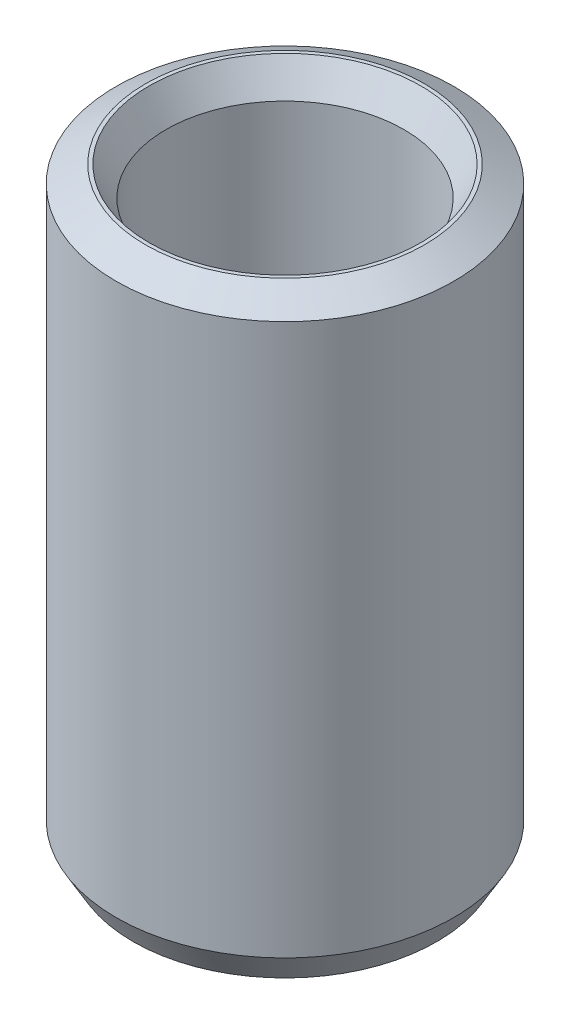
SolidWorks part; units mm, degrees
ref_plane "Front Plane" through (0, 0, 0) normal (0, 0, 1) x (1, 0, 0)
ref_plane "Top Plane" through (0, 0, 0) normal (0, 1, 0) x (1, 0, 0)
ref_plane "Right Plane" through (0, 0, 0) normal (1, 0, 0) x (0, 0, -1)
sketch "Sketch1" plane through (0, 0, 0) normal (0, 1, 0) x (1, 0, 0)
  circle A0 centre (0, 0) radius 15
  dimension "SLEEVE_OD" = 30
extrude "Boss-Extrude1" add sketch "Sketch1" along normal blind 53.0629
sketch "Sketch2" plane through (0, 0, 0) normal (0, 1, 0) x (1, 0, 0)
  circle A0 centre (0, 0) radius 10.5672
  dimension "BORE_D" = 21.1343
extrude "Cut-Extrude1" cut sketch "Sketch2" along normal through all
chamfer "Chamfer1" distance 1.5037 angle 60 4 edges at (0, 53.0629, 10.5672) (0, 0, 10.5672) (0, 0, 15) (0, 53.0629, 15) first distance on face at (0, 53.0629, 10.5672) first distance on face at (0, 0, 10.5672) first distance on face at (0, 53.0629, 15)
